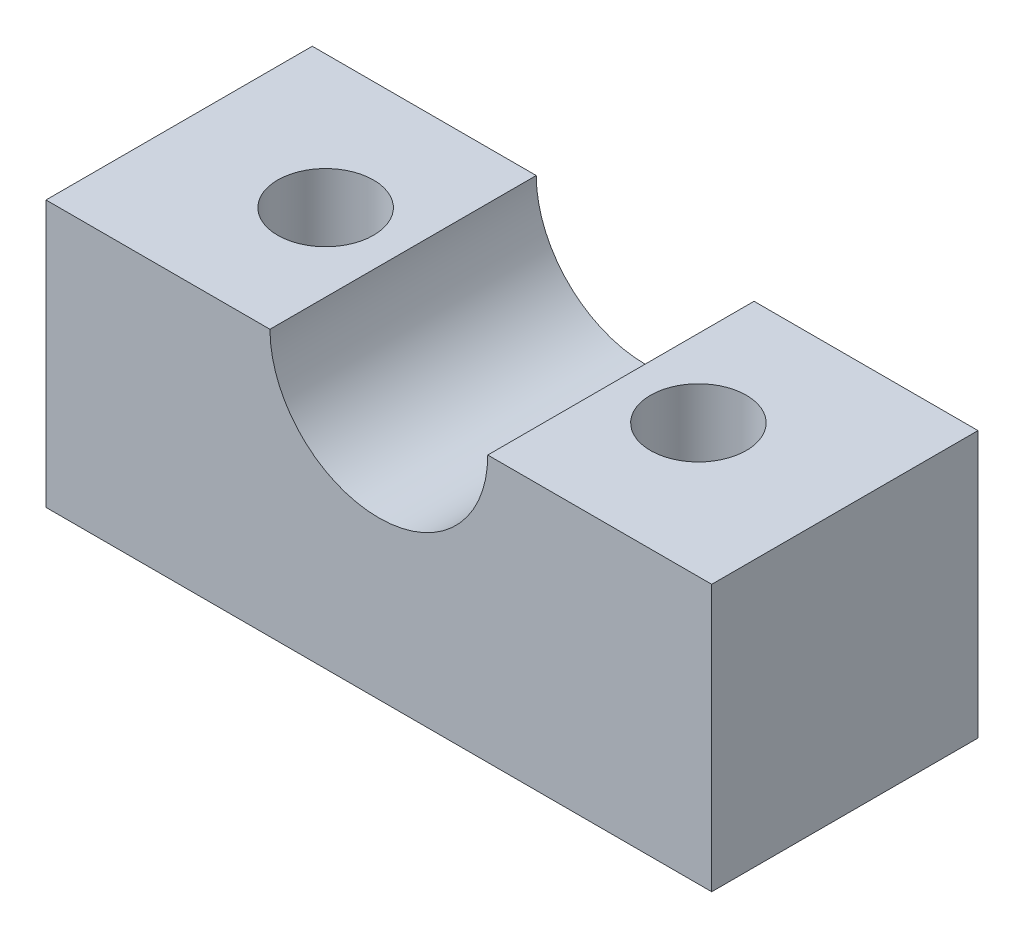
SolidWorks part; units mm, degrees
ref_plane "Piano frontale" through (0, 0, 0) normal (0, 0, 1) x (1, 0, 0)
ref_plane "Piano superiore" through (0, 0, 0) normal (0, 1, 0) x (1, 0, 0)
ref_plane "Piano destro" through (0, 0, 0) normal (1, 0, 0) x (0, 0, -1)
sketch "Schizzo1" plane through (0, 0, 0) normal (0, 0, 1) x (1, 0, 0)
  line L0 (0, 5) -> (0, -5) construction
  line L1 (-12.5, -5) -> (12.5, -5)
  line L2 (-12.5, -5) -> (-12.5, 5)
  line L3 (-12.5, 5) -> (-4.09, 5)
  line L4 (12.5, -5) -> (12.5, 5)
  line L5 (-12.5, -5) -> (12.5, 5) construction
  line L6 (-12.5, 5) -> (12.5, -5) construction
  line L7 (4.09, 5) -> (12.5, 5)
  line L8 (-4.09, 5) -> (4.09, 5) construction
  arc A0 (-4.09, 5) -> (4.09, 5) centre (0, 5) ccw
  point P0 (0, 0)
  dimension "D3" = 4.09
  dimension "D1" = 10
  dimension "D2" = 25
extrude "Main body" add sketch "Schizzo1" along normal mid plane 10 contours L7 L4 L1 L2 L3 A0
sketch "Schizzo2" plane through (0, -5, 0) normal (0, -1, 0) x (1, 0, 0)
  line L0 (0, 5) -> (0, -5) construction
  line L1 (-12.5, 5) -> (12.5, 5) construction
  line L2 (-12.5, -5) -> (12.5, -5) construction
  line L3 (-12.5, 0) -> (12.5, 0) construction
  line L4 (-12.5, 5) -> (-12.5, -5) construction
  line L5 (12.5, 5) -> (12.5, -5) construction
  circle A0 centre (-7, 0) radius 1.8
  circle A1 centre (7, 0) radius 1.8
  dimension "D2" = 3.6
  dimension "D1" = 7
extrude "screw holes" cut sketch "Schizzo2" against normal up to next contours A0 | A1
ref_axis "y rod axis" through (0, 5, 5) along (0, 0, -1)
ref_axis "Screw1 hole" through (7, 5, 0) along (0, -1, 0)
ref_axis "Screw 2 hole" through (-7, 5, 0) along (0, -1, 0)
